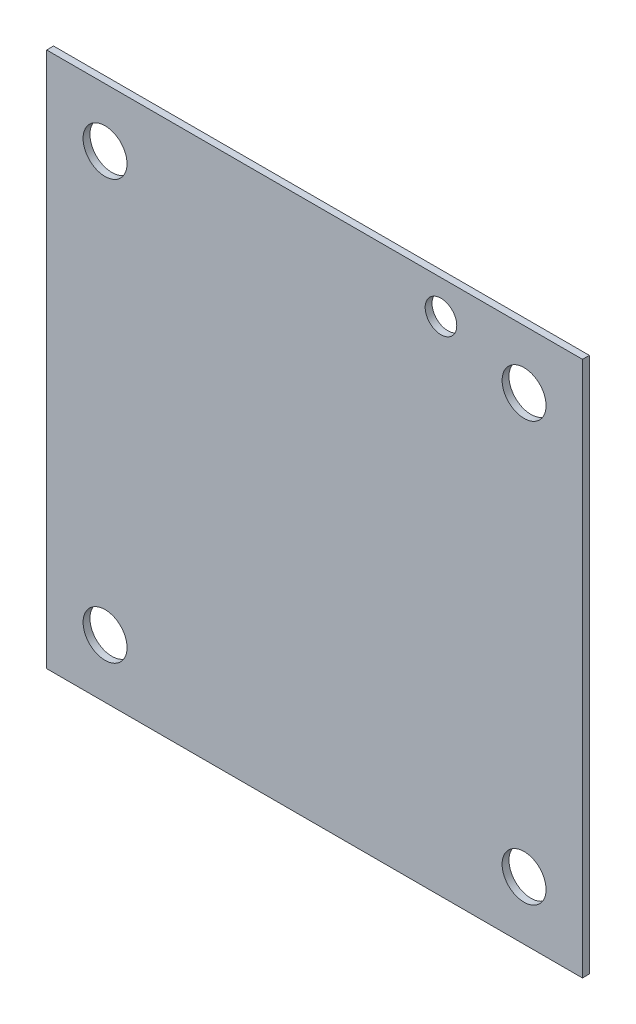
SolidWorks part; units mm, degrees
ref_plane "Front Plane" through (0, 0, 0) normal (0, 0, 1) x (1, 0, 0)
ref_plane "Top Plane" through (0, 0, 0) normal (0, 1, 0) x (1, 0, 0)
ref_plane "Right Plane" through (0, 0, 0) normal (1, 0, 0) x (0, 0, -1)
sketch "Sketch1" plane through (0, 0, 0) normal (0, 0, 1) x (1, 0, 0)
  line L1 (-19.5, -19.5) -> (19.5, -19.5)
  line L2 (-19.5, -19.5) -> (-19.5, 19.5)
  line L3 (-19.5, 19.5) -> (19.5, 19.5)
  line L4 (19.5, -19.5) -> (19.5, 19.5)
  line L5 (-19.5, -19.5) -> (19.5, 19.5) construction
  line L6 (-19.5, 19.5) -> (19.5, -19.5) construction
  line L12 (19.5, -19.5) -> (19.5, -7.325)
  line L13 (19.5, -7.325) -> (17.7, -7.325)
  line L14 (17.7, -7.325) -> (17.7, -11.5758)
  line L15 (11.5029, -17.4996) -> (-11.5029, -17.4996)
  line L16 (-17.7, -11.5758) -> (-17.7, 11.5758)
  line L17 (-11.5029, 17.4996) -> (6.0985, 17.4996)
  line L18 (17.7, 11.5758) -> (17.7, 4.675)
  line L19 (17.7, 4.675) -> (19.5, 4.675)
  line L20 (19.5, 4.675) -> (19.5, 35.2)
  line L21 (15.5, 39.2) -> (-15.5, 39.2)
  line L22 (-19.5, 35.2) -> (-19.5, -19.5)
  line L23 (-19.5, -19.5) -> (19.5, -19.5)
  line L24 (19.5, -19.5) -> (19.5, -7.325)
  line L25 (19.5, -7.325) -> (17.7, -7.325)
  line L26 (17.7, -7.325) -> (17.7, -11.5758)
  line L27 (11.5029, -17.4996) -> (-11.5029, -17.4996)
  line L28 (-17.7, -11.5758) -> (-17.7, 11.5758)
  line L29 (-11.5029, 17.4996) -> (6.0985, 17.4996)
  line L30 (17.7, 11.5758) -> (17.7, 4.675)
  line L31 (17.7, 4.675) -> (19.5, 4.675)
  line L32 (19.5, 4.675) -> (19.5, 35.2)
  line L33 (15.5, 39.2) -> (-15.5, 39.2)
  line L34 (-19.5, 35.2) -> (-19.5, -19.5)
  line L35 (-19.5, -19.5) -> (19.5, -19.5)
  circle A0 centre (-15.25, -15.25) radius 1.6 construction
  circle A1 centre (-15.25, 15.25) radius 1.6 construction
  circle A2 centre (9.2, 17.05) radius 1.15 construction
  circle A3 centre (15.25, 15.25) radius 1.6 construction
  circle A4 centre (15.25, -15.25) radius 1.6 construction
  circle A5 centre (-15.25, -15.25) radius 1.6
  circle A6 centre (-15.25, 15.25) radius 1.6
  circle A7 centre (9.2, 17.05) radius 1.15
  circle A8 centre (15.25, 15.25) radius 1.6
  circle A9 centre (15.25, -15.25) radius 1.6
  arc A16 (16.3329, -12.506) -> (17.7, -11.5758) centre (16.7, -11.5758) ccw
  arc A17 (16.3329, -12.506) -> (12.4515, -16.1832) centre (15.25, -15.25) ccw
  arc A18 (11.5029, -17.4996) -> (12.4515, -16.1832) centre (11.5029, -16.4996) ccw
  arc A19 (-12.4515, -16.1832) -> (-11.5029, -17.4996) centre (-11.5029, -16.4996) ccw
  arc A20 (-12.4515, -16.1832) -> (-16.3329, -12.506) centre (-15.25, -15.25) ccw
  arc A21 (-17.7, -11.5758) -> (-16.3329, -12.506) centre (-16.7, -11.5758) ccw
  arc A22 (-16.3329, 12.506) -> (-17.7, 11.5758) centre (-16.7, 11.5758) ccw
  arc A23 (-16.3329, 12.506) -> (-12.4515, 16.1832) centre (-15.25, 15.25) ccw
  arc A24 (-11.5029, 17.4996) -> (-12.4515, 16.1832) centre (-11.5029, 16.4996) ccw
  arc A25 (7.0831, 16.6743) -> (6.0985, 17.4996) centre (6.0985, 16.4996) ccw
  arc A26 (7.0831, 16.6743) -> (10.6565, 15.4685) centre (9.2, 17.05) ccw
  arc A27 (12.3254, 14.8639) -> (10.6565, 15.4685) centre (11.334, 14.733) ccw
  arc A28 (12.3254, 14.8639) -> (16.3329, 12.506) centre (15.25, 15.25) ccw
  arc A29 (17.7, 11.5758) -> (16.3329, 12.506) centre (16.7, 11.5758) ccw
  arc A30 (19.5, 35.2) -> (15.5, 39.2) centre (15.5, 35.2) ccw
  arc A31 (-15.5, 39.2) -> (-19.5, 35.2) centre (-15.5, 35.2) ccw
  arc A32 (16.3329, -12.506) -> (17.7, -11.5758) centre (16.7, -11.5758) ccw
  arc A33 (16.3329, -12.506) -> (12.4515, -16.1832) centre (15.25, -15.25) ccw
  arc A34 (11.5029, -17.4996) -> (12.4515, -16.1832) centre (11.5029, -16.4996) ccw
  arc A35 (-12.4515, -16.1832) -> (-11.5029, -17.4996) centre (-11.5029, -16.4996) ccw
  arc A36 (-12.4515, -16.1832) -> (-16.3329, -12.506) centre (-15.25, -15.25) ccw
  arc A37 (-17.7, -11.5758) -> (-16.3329, -12.506) centre (-16.7, -11.5758) ccw
  arc A38 (-16.3329, 12.506) -> (-17.7, 11.5758) centre (-16.7, 11.5758) ccw
  arc A39 (-16.3329, 12.506) -> (-12.4515, 16.1832) centre (-15.25, 15.25) ccw
  arc A40 (-11.5029, 17.4996) -> (-12.4515, 16.1832) centre (-11.5029, 16.4996) ccw
  arc A41 (7.0831, 16.6743) -> (6.0985, 17.4996) centre (6.0985, 16.4996) ccw
  arc A42 (7.0831, 16.6743) -> (10.6565, 15.4685) centre (9.2, 17.05) ccw
  arc A43 (12.3254, 14.8639) -> (10.6565, 15.4685) centre (11.334, 14.733) ccw
  arc A44 (12.3254, 14.8639) -> (16.3329, 12.506) centre (15.25, 15.25) ccw
  arc A45 (17.7, 11.5758) -> (16.3329, 12.506) centre (16.7, 11.5758) ccw
  arc A46 (19.5, 35.2) -> (15.5, 39.2) centre (15.5, 35.2) ccw
  arc A47 (-15.5, 39.2) -> (-19.5, 35.2) centre (-15.5, 35.2) ccw
  point P27 (0, 0)
  dimension "D1" = 0
extrude "Boss-Extrude1" add sketch "Sketch1" along normal blind 0.5 contours A45 L30 L31 L4 L3 L2 L1 L25 L26 A32 A33 A34 L27 A35 A36 A37 L28 A38 A39 A40 L29 A41 A42 A43 A44 A9 A8 A7 A6 A5 | L30 A45 A44 A43 A42 A41 L29 A40 A39 A38 L28 A37 A36 A35 L27 A34 A33 A32 L26 L25 L4 L31 region at (-18.9485, 0, 0) region at (0.2534, -0.1902, 0)
